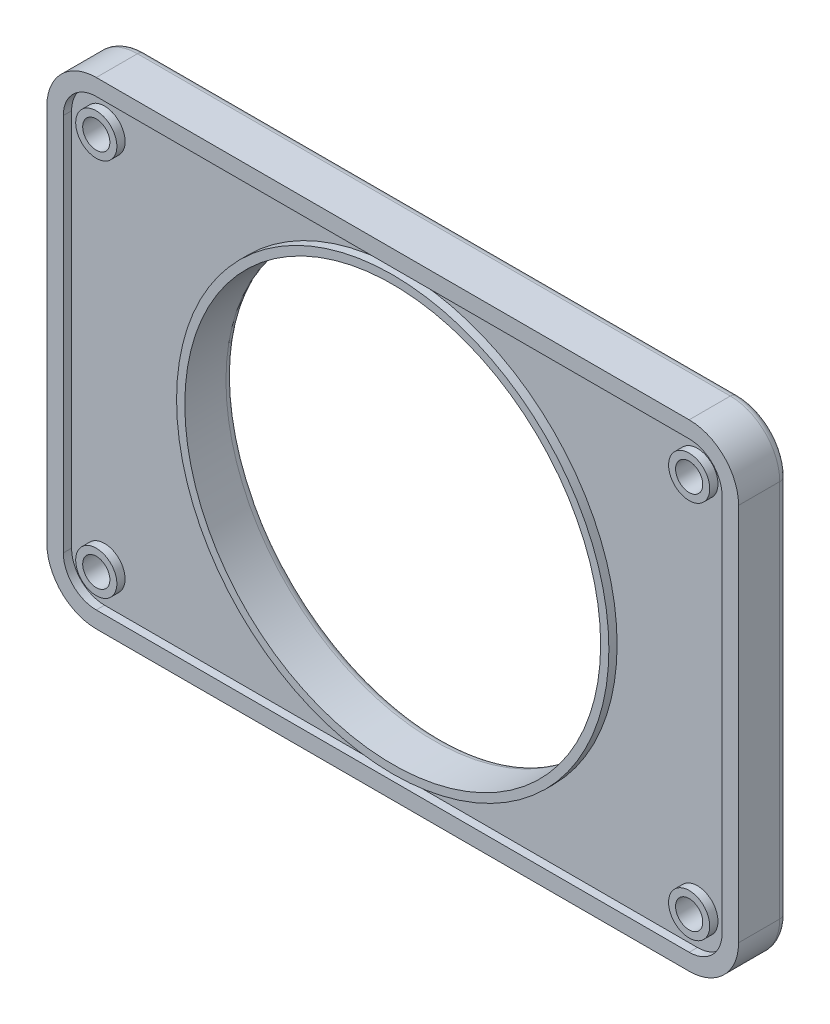
SolidWorks part; units mm, degrees
ref_plane "前视基准面" through (0, 0, 0) normal (0, 0, 1) x (1, 0, 0)
ref_plane "上视基准面" through (0, 0, 0) normal (0, 1, 0) x (1, 0, 0)
ref_plane "右视基准面" through (0, 0, 0) normal (1, 0, 0) x (0, 0, -1)
sketch "草图1" plane through (0, 0, 0) normal (0, 0, 1) x (1, 0, 0)
  line L1 (-36, 29) -> (36, 29)
  line L2 (-42, 23) -> (-42, -23)
  line L3 (-36, -29) -> (36, -29)
  line L4 (42, 23) -> (42, -23)
  line L5 (-42, 29) -> (42, -29) construction
  line L6 (-42, -29) -> (42, 29) construction
  circle A0 centre (0, 0) radius 25.25
  arc A1 (36, 29) -> (42, 23) centre (36, 23) cw
  arc A2 (36, -29) -> (42, -23) centre (36, -23) ccw
  arc A3 (-42, -23) -> (-36, -29) centre (-36, -23) ccw
  arc A4 (-36, 29) -> (-42, 23) centre (-36, 23) ccw
  point P0 (0, 0)
  dimension "D3" = 50.5
  dimension "D4" = 6
  dimension "D1" = 84
  dimension "D2" = 58
extrude "凸台-拉伸1" add sketch "草图1" along normal blind 5
sketch "草图2" plane through (0, 0, 5) normal (0, 0, 1) x (1, 0, 0)
  line L4 (36, 29) -> (-36, 29)
  line L5 (-42, 23) -> (-42, -23)
  line L6 (-36, -29) -> (36, -29)
  line L7 (42, -23) -> (42, 23)
  line L8 (36, 29) -> (-36, 29)
  line L9 (-42, 23) -> (-42, -23)
  line L10 (-36, -29) -> (36, -29)
  line L11 (42, -23) -> (42, 23)
  circle A0 centre (0, 0) radius 23.85
  arc A5 (42, 23) -> (36, 29) centre (36, 23) ccw
  arc A6 (-36, 29) -> (-42, 23) centre (-36, 23) ccw
  arc A7 (-42, -23) -> (-36, -29) centre (-36, -23) ccw
  arc A8 (36, -29) -> (42, -23) centre (36, -23) ccw
  arc A9 (42, 23) -> (36, 29) centre (36, 23) ccw
  arc A10 (-36, 29) -> (-42, 23) centre (-36, 23) ccw
  arc A11 (-42, -23) -> (-36, -29) centre (-36, -23) ccw
  arc A12 (36, -29) -> (42, -23) centre (36, -23) ccw
  dimension "D1" = 47.7
  dimension "D2" = 0
extrude "凸台-拉伸2" add sketch "草图2" along normal blind 1
chamfer "倒角2" distance 0.5 angle 45 1 edges at (23.85, 0, 5)
sketch "草图3" plane through (0, 0, 6) normal (0, 0, 1) x (1, 0, 0)
  line L12 (36, 27) -> (-36, 27)
  line L13 (-40, 23) -> (-40, -23)
  line L14 (-36, -27) -> (36, -27)
  line L15 (40, -23) -> (40, 23)
  line L16 (36, 27) -> (-36, 27)
  line L17 (-40, 23) -> (-40, -23)
  line L18 (-36, -27) -> (36, -27)
  line L19 (40, -23) -> (40, 23)
  arc A12 (40, 23) -> (36, 27) centre (36, 23) ccw
  arc A13 (-36, 27) -> (-40, 23) centre (-36, 23) ccw
  arc A14 (-40, -23) -> (-36, -27) centre (-36, -23) ccw
  arc A15 (36, -27) -> (40, -23) centre (36, -23) ccw
  arc A16 (40, 23) -> (36, 27) centre (36, 23) ccw
  arc A17 (-36, 27) -> (-40, 23) centre (-36, 23) ccw
  arc A18 (-40, -23) -> (-36, -27) centre (-36, -23) ccw
  arc A19 (36, -27) -> (40, -23) centre (36, -23) ccw
  dimension "D1" = 2
extrude "切除-拉伸1" cut sketch "草图3" against normal blind 1
sketch "草图4" plane through (0, 0, 5) normal (0, 0, 1) x (1, 0, 0)
  circle A1 centre (0, 0) radius 25.25 construction
  circle A2 centre (0, 0) radius 26.25
  circle A3 centre (0, 0) radius 26.25
  circle A4 centre (0, 0) radius 25.25
  dimension "D1" = 1
extrude "凸台-拉伸3" add sketch "草图4" along normal blind 1
sketch "草图5" plane through (0, 0, 5) normal (0, 0, 1) x (1, 0, 0)
  line L0 (0, 0) -> (48.7001, 0) construction
  line L1 (0, 0) -> (0, 30.608) construction
  circle A0 centre (36, 23) radius 2.5
  circle A1 centre (36, -23) radius 2.5
  circle A2 centre (-36, 23) radius 2.5
  circle A3 centre (-36, -23) radius 2.5
  dimension "D1" = 5
extrude "凸台-拉伸4" add sketch "草图5" along normal up to surface (1 mm away) up to face at (0, 0, 6)
sketch "草图6" plane through (0, 0, 6) normal (0, 0, 1) x (1, 0, 0)
  line L0 (0, 0) -> (48.7472, 0) construction
  line L1 (0, 0) -> (0, 20.1483) construction
  circle A0 centre (36, 23) radius 1.65
  circle A1 centre (36, -23) radius 1.65
  circle A2 centre (-36, 23) radius 1.65
  circle A3 centre (-36, -23) radius 1.65
  dimension "D1" = 3.3
extrude "切除-拉伸2" cut sketch "草图6" against normal blind 3.5
fillet "圆角2" radius 1 9 edges at (25.25, 0, 0) (0, 29, 0) (-40.2426, 27.2426, 0) (-42, 0, 0) (-40.2426, -27.2426, 0) (0, -29, 0) (40.2426, -27.2426, 0) (42, 0, 0) (40.2426, 27.2426, 0)
